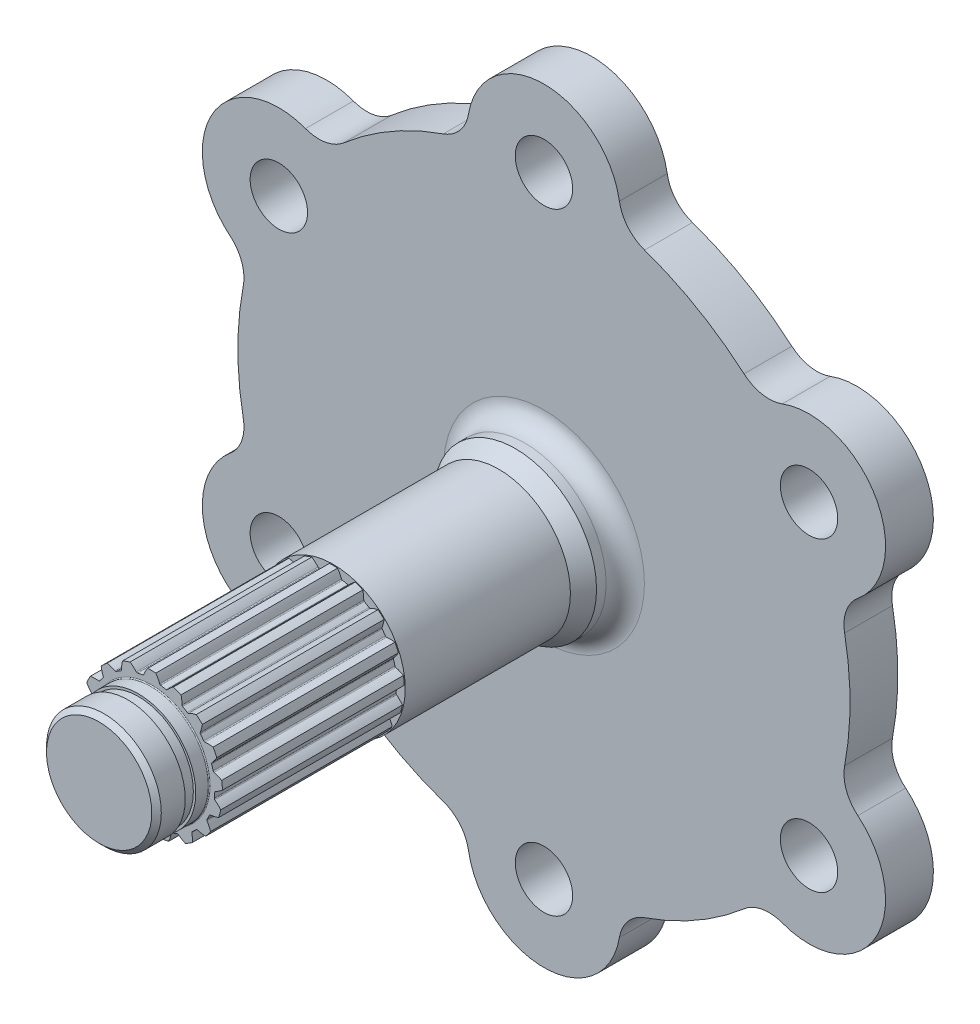
SolidWorks part; units mm, degrees
material "7075-O (SS)"
ref_plane "Front Plane" through (0, 0, 0) normal (0, 0, 1) x (1, 0, 0)
ref_plane "Top Plane" through (0, 0, 0) normal (0, 1, 0) x (1, 0, 0)
ref_plane "Right Plane" through (0, 0, 0) normal (1, 0, 0) x (0, 0, -1)
sketch "Sketch1" plane through (0, 0, 0) normal (0, 0, 1) x (1, 0, 0)
  line L0 (0, -55) -> (0, 55) construction
  line L1 (0, 40) -> (0, 0) construction
  line L2 (0, 0) -> (0, -40) construction
  circle A1 centre (0, 32) radius 3
  circle A2 centre (0, 0) radius 41.3
  circle A3 centre (27.7128, 16) radius 3
  circle A4 centre (0, 0) radius 41.3
  circle A5 centre (27.7128, -16) radius 3
  circle A6 centre (0, 0) radius 41.3
  circle A7 centre (0, -32) radius 3
  circle A8 centre (0, 0) radius 41.3
  circle A9 centre (-27.7128, -16) radius 3
  circle A10 centre (0, 0) radius 41.3
  circle A11 centre (-27.7128, 16) radius 3
  arc A12 (-7.9373, 31) -> (-22.8782, 22.3739) centre (0, 0) ccw
  arc A13 (7.9373, 31) -> (-7.9373, 31) centre (0, 32) ccw
  arc A14 (30.8154, 8.6261) -> (22.8782, 22.3739) centre (27.7128, 16) ccw
  arc A15 (22.8782, -22.3739) -> (30.8154, -8.6261) centre (27.7128, -16) ccw
  arc A16 (-7.9373, -31) -> (7.9373, -31) centre (0, -32) ccw
  arc A17 (-30.8154, -8.6261) -> (-22.8782, -22.3739) centre (-27.7128, -16) ccw
  arc A18 (-22.8782, 22.3739) -> (-30.8154, 8.6261) centre (-27.7128, 16) ccw
  circle A19 centre (0, 32) radius 8 construction
  arc A20 (-22.8782, -22.3739) -> (-7.9373, -31) centre (0, 0) ccw
  arc A21 (30.8154, -8.6261) -> (30.8154, 8.6261) centre (0, 0) ccw
  arc A22 (-30.8154, 8.6261) -> (-30.8154, -8.6261) centre (0, 0) ccw
  arc A23 (7.9373, -31) -> (22.8782, -22.3739) centre (0, 0) ccw
  arc A25 (22.8782, 22.3739) -> (7.9373, 31) centre (0, 0) ccw
  point P25 (0, 0)
  point P38 (0, 0)
  dimension "D1" = 32
  dimension "D5" = 6
  dimension "D6" = 64
  dimension "D3" = 5
  dimension "D2" = 6
  dimension "D4" = 6
extrude "Boss-Extrude1" add sketch "Sketch1" along normal blind 5 contours A11 A9 A7 A5 A3 A1 region at (0, 0, 0)
sketch "Sketch3" plane through (0, 0, 5) normal (0, 0, 1) x (1, 0, 0)
  circle A0 centre (0, 0) radius 7.5
  dimension "D1" = 15
extrude "Boss-Extrude2" add sketch "Sketch3" along normal blind 22
sketch "Sketch9" plane through (0, 0, 27) normal (0, 0, 1) x (1, 0, 0)
  arc A42 (3.0654, 6.727) -> (2.2666, 7.0365) centre (0, 0) ccw
  arc A43 (1.4878, 6.4262) -> (1.2121, 6.4839) centre (0, 0) ccw
  arc A44 (1.2121, 6.4839) -> (0.9342, 6.5297) centre (0, 0) ccw
  arc A45 (0.4284, 7.3801) -> (-0.4283, 7.3801) centre (0, 0) ccw
  arc A46 (-0.9341, 6.5297) -> (-1.212, 6.4839) centre (0, 0) ccw
  arc A47 (-1.212, 6.4839) -> (-1.4877, 6.4262) centre (0, 0) ccw
  arc A48 (-2.2665, 7.0365) -> (-3.0654, 6.727) centre (0, 0) ccw
  arc A49 (-3.2298, 5.7513) -> (-3.4724, 5.6082) centre (0, 0) ccw
  arc A50 (-3.4724, 5.6082) -> (-3.7087, 5.4549) centre (0, 0) ccw
  arc A51 (-4.6554, 5.7425) -> (-5.2885, 5.1654) centre (0, 0) ccw
  arc A52 (-5.0894, 4.1962) -> (-5.2639, 3.9751) centre (0, 0) ccw
  arc A53 (-5.2639, 3.9751) -> (-5.4288, 3.7468) centre (0, 0) ccw
  arc A54 (-6.4154, 3.6731) -> (-6.7973, 2.9062) centre (0, 0) ccw
  arc A55 (-6.2615, 2.0744) -> (-6.3444, 1.8052) centre (0, 0) ccw
  arc A56 (-6.3444, 1.8052) -> (-6.4156, 1.5327) centre (0, 0) ccw
  arc A57 (-7.3091, 1.1075) -> (-7.3881, 0.2544) centre (0, 0) ccw
  arc A58 (-6.588, -0.3276) -> (-6.568, -0.6086) centre (0, 0) ccw
  arc A59 (-6.568, -0.6086) -> (-6.5361, -0.8884) centre (0, 0) ccw
  arc A60 (-7.2156, -1.6076) -> (-6.9811, -2.4316) centre (0, 0) ccw
  arc A61 (-6.0248, -2.6854) -> (-5.9046, -2.9401) centre (0, 0) ccw
  arc A62 (-5.9046, -2.9401) -> (-5.7737, -3.1895) centre (0, 0) ccw
  arc A63 (-6.1476, -4.1056) -> (-5.6313, -4.7893) centre (0, 0) ccw
  arc A64 (-4.6479, -4.6805) -> (-4.4438, -4.8746) centre (0, 0) ccw
  arc A65 (-4.4438, -4.8746) -> (-4.2317, -5.0599) centre (0, 0) ccw
  arc A66 (-4.2493, -6.0491) -> (-3.5209, -6.5001) centre (0, 0) ccw
  arc A67 (-2.6432, -6.0434) -> (-2.3828, -6.1507) centre (0, 0) ccw
  arc A68 (-2.3828, -6.1507) -> (-2.1181, -6.2469) centre (0, 0) ccw
  arc A69 (-1.7771, -7.1757) -> (-0.935, -7.3331) centre (0, 0) ccw
  arc A70 (-0.2816, -6.5901) -> (0, -6.5962) centre (0, 0.0001) ccw
  arc A71 (0, -6.5962) -> (0.2816, -6.5901) centre (0, 0.0001) ccw
  arc A72 (0.935, -7.3331) -> (1.7772, -7.1757) centre (0, 0) ccw
  arc A73 (2.1181, -6.2469) -> (2.3828, -6.1507) centre (0, 0) ccw
  arc A74 (2.3828, -6.1507) -> (2.6432, -6.0434) centre (0, 0) ccw
  arc A75 (3.5209, -6.5001) -> (4.2493, -6.0491) centre (0, 0) ccw
  arc A76 (4.2317, -5.0599) -> (4.4438, -4.8746) centre (0, 0) ccw
  arc A77 (4.4438, -4.8746) -> (4.6479, -4.6805) centre (0, 0) ccw
  arc A78 (5.6313, -4.7893) -> (6.1476, -4.1056) centre (0, 0) ccw
  arc A79 (5.7738, -3.1895) -> (5.9047, -2.9401) centre (0, 0) ccw
  arc A80 (5.9047, -2.9401) -> (6.0248, -2.6854) centre (0, 0) ccw
  arc A81 (6.9811, -2.4316) -> (7.2156, -1.6076) centre (0, 0) ccw
  arc A82 (6.5361, -0.8884) -> (6.5681, -0.6086) centre (0, 0) ccw
  arc A83 (6.5681, -0.6086) -> (6.5881, -0.3276) centre (0, 0) ccw
  arc A84 (7.3881, 0.2544) -> (7.3091, 1.1075) centre (0, 0) ccw
  arc A85 (6.4157, 1.5327) -> (6.3444, 1.8052) centre (0, 0) ccw
  arc A86 (6.3444, 1.8052) -> (6.2615, 2.0744) centre (0, 0) ccw
  arc A87 (6.7973, 2.9062) -> (6.4155, 3.6731) centre (0, 0) ccw
  arc A88 (5.4288, 3.7468) -> (5.2639, 3.9751) centre (0, 0) ccw
  arc A89 (5.2639, 3.9751) -> (5.0894, 4.1962) centre (0, 0) ccw
  arc A90 (5.2885, 5.1654) -> (4.6554, 5.7425) centre (0, 0) ccw
  arc A91 (3.7087, 5.4549) -> (3.4725, 5.6082) centre (0, 0) ccw
  arc A92 (3.4725, 5.6082) -> (3.2299, 5.7513) centre (0, 0) ccw
  spline S0 degree 3 poles (3.2299, 5.7513) (3.2097, 5.7626) (3.1758, 5.7963) (3.1637, 5.8426) (3.1639, 5.8657) knots 0 0 0 0 0.499566 1 1 1 1
  spline S1 degree 6 poles (3.1639, 5.8657) (3.1648, 5.9848) (3.1603, 6.1142) (3.1493, 6.2536) (3.1305, 6.4026) (3.1029, 6.5607) (3.0654, 6.727) knots 0 0 0 0 0 0 0 1 1 1 1 1 1 1
  spline S2 degree 6 poles (2.2666, 7.0365) (2.1268, 6.9388) (2, 6.8406) (1.8857, 6.7431) (1.7836, 6.6475) (1.6931, 6.5549) (1.6136, 6.4663) knots 0 0 0 0 0 0 0 1 1 1 1 1 1 1
  spline S3 degree 3 poles (1.6136, 6.4663) (1.5982, 6.4491) (1.558, 6.423) (1.5102, 6.421) (1.4878, 6.4262) knots 0 0 0 0 0.500434 1 1 1 1
  spline S4 degree 3 poles (0.9342, 6.5297) (0.9113, 6.5329) (0.8675, 6.5521) (0.8395, 6.5909) (0.8313, 6.6126) knots 0 0 0 0 0.499566 1 1 1 1
  spline S5 degree 6 poles (0.8313, 6.6126) (0.7891, 6.7239) (0.7382, 6.8429) (0.6775, 6.969) (0.6062, 7.1011) (0.5234, 7.2385) (0.4284, 7.3801) knots 0 0 0 0 0 0 0 1 1 1 1 1 1 1
  spline S6 degree 6 poles (-0.4283, 7.3801) (-0.5234, 7.2385) (-0.6062, 7.1011) (-0.6775, 6.969) (-0.7382, 6.8429) (-0.7891, 6.7239) (-0.8313, 6.6126) knots 0 0 0 0 0 0 0 1 1 1 1 1 1 1
  spline S7 degree 3 poles (-0.8313, 6.6126) (-0.8394, 6.5909) (-0.8674, 6.5521) (-0.9113, 6.5329) (-0.9341, 6.5297) knots 0 0 0 0 0.500434 1 1 1 1
  spline S8 degree 3 poles (-1.4877, 6.4262) (-1.5102, 6.421) (-1.558, 6.423) (-1.5981, 6.4491) (-1.6135, 6.4663) knots 0 0 0 0 0.499566 1 1 1 1
  spline S9 degree 6 poles (-1.6135, 6.4663) (-1.6931, 6.5549) (-1.7836, 6.6475) (-1.8857, 6.7431) (-1.9999, 6.8406) (-2.1268, 6.9388) (-2.2665, 7.0365) knots 0 0 0 0 0 0 0 1 1 1 1 1 1 1
  spline S10 degree 6 poles (-3.0654, 6.727) (-3.1029, 6.5607) (-3.1305, 6.4026) (-3.1492, 6.2536) (-3.1603, 6.1142) (-3.1648, 5.9848) (-3.1639, 5.8657) knots 0 0 0 0 0 0 0 1 1 1 1 1 1 1
  spline S11 degree 3 poles (-3.1639, 5.8657) (-3.1637, 5.8426) (-3.1757, 5.7963) (-3.2097, 5.7626) (-3.2298, 5.7513) knots 0 0 0 0 0.500434 1 1 1 1
  spline S12 degree 3 poles (-3.7087, 5.4549) (-3.7277, 5.4418) (-3.7731, 5.4265) (-3.8199, 5.4363) (-3.8405, 5.4468) knots 0 0 0 0 0.499566 1 1 1 1
  spline S13 degree 6 poles (-3.8405, 5.4468) (-3.9467, 5.5007) (-4.0645, 5.5543) (-4.1942, 5.6066) (-4.336, 5.6562) (-4.4897, 5.7019) (-4.6554, 5.7425) knots 0 0 0 0 0 0 0 1 1 1 1 1 1 1
  spline S14 degree 6 poles (-5.2885, 5.1654) (-5.2633, 4.9967) (-5.232, 4.8394) (-5.1956, 4.6937) (-5.1556, 4.5597) (-5.113, 4.4374) (-5.0692, 4.3267) knots 0 0 0 0 0 0 0 1 1 1 1 1 1 1
  spline S15 degree 3 poles (-5.0692, 4.3267) (-5.0606, 4.3052) (-5.0552, 4.2577) (-5.0746, 4.214) (-5.0894, 4.1962) knots 0 0 0 0 0.500434 1 1 1 1
  spline S16 degree 3 poles (-5.4288, 3.7468) (-5.4418, 3.7278) (-5.4785, 3.6971) (-5.5257, 3.6893) (-5.5487, 3.6917) knots 0 0 0 0 0.499566 1 1 1 1
  spline S17 degree 6 poles (-5.5487, 3.6917) (-5.6672, 3.7035) (-5.7965, 3.711) (-5.9363, 3.7128) (-6.0864, 3.7079) (-6.2463, 3.695) (-6.4154, 3.6731) knots 0 0 0 0 0 0 0 1 1 1 1 1 1 1
  spline S18 degree 6 poles (-6.7973, 2.9062) (-6.7129, 2.758) (-6.6268, 2.6226) (-6.5403, 2.4998) (-6.4546, 2.3894) (-6.3707, 2.2907) (-6.2898, 2.2033) knots 0 0 0 0 0 0 0 1 1 1 1 1 1 1
  spline S19 degree 3 poles (-6.2898, 2.2033) (-6.2741, 2.1864) (-6.2518, 2.144) (-6.2542, 2.0962) (-6.2615, 2.0744) knots 0 0 0 0 0.500434 1 1 1 1
  spline S20 degree 3 poles (-6.4156, 1.5327) (-6.421, 1.5102) (-6.4441, 1.4683) (-6.4853, 1.444) (-6.5076, 1.4379) knots 0 0 0 0 0.499566 1 1 1 1
  spline S21 degree 6 poles (-6.5076, 1.4379) (-6.6224, 1.4062) (-6.7456, 1.3665) (-6.8767, 1.3177) (-7.0149, 1.2588) (-7.1593, 1.1891) (-7.3091, 1.1075) knots 0 0 0 0 0 0 0 1 1 1 1 1 1 1
  spline S22 degree 6 poles (-7.3881, 0.2544) (-7.2559, 0.1468) (-7.1267, 0.0516) (-7.0017, -0.0316) (-6.8818, -0.1036) (-6.768, -0.1653) (-6.661, -0.2176) knots 0 0 0 0 0 0 0 1 1 1 1 1 1 1
  spline S23 degree 3 poles (-6.661, -0.2176) (-6.6402, -0.2277) (-6.6042, -0.2592) (-6.5891, -0.3046) (-6.588, -0.3276) knots 0 0 0 0 0.500434 1 1 1 1
  spline S24 degree 3 poles (-6.5361, -0.8884) (-6.5329, -0.9113) (-6.5394, -0.9587) (-6.569, -0.9963) (-6.5876, -1.01) knots 0 0 0 0 0.499566 1 1 1 1
  spline S25 degree 6 poles (-6.5876, -1.01) (-6.6831, -1.081) (-6.7837, -1.1626) (-6.8883, -1.2555) (-6.9959, -1.3602) (-7.1054, -1.4775) (-7.2156, -1.6076) knots 0 0 0 0 0 0 0 1 1 1 1 1 1 1
  spline S26 degree 6 poles (-6.9811, -2.4316) (-6.8189, -2.4843) (-6.6641, -2.5263) (-6.5175, -2.5588) (-6.3797, -2.5826) (-6.2512, -2.5991) (-6.1326, -2.6092) knots 0 0 0 0 0 0 0 1 1 1 1 1 1 1
  spline S27 degree 3 poles (-6.1326, -2.6092) (-6.1096, -2.6111) (-6.0646, -2.6274) (-6.0341, -2.6643) (-6.0248, -2.6854) knots 0 0 0 0 0.500434 1 1 1 1
  spline S28 degree 3 poles (-5.7737, -3.1895) (-5.7625, -3.2097) (-5.7514, -3.2563) (-5.7655, -3.302) (-5.7779, -3.3215) knots 0 0 0 0 0.499566 1 1 1 1
  spline S29 degree 6 poles (-5.7779, -3.3215) (-5.8413, -3.4223) (-5.9056, -3.5347) (-5.9696, -3.659) (-6.0321, -3.7956) (-6.0918, -3.9445) (-6.1476, -4.1056) knots 0 0 0 0 0 0 0 1 1 1 1 1 1 1
  spline S30 degree 6 poles (-5.6313, -4.7893) (-5.461, -4.7798) (-5.3015, -4.7631) (-5.153, -4.7404) (-5.0159, -4.7128) (-4.8902, -4.6818) (-4.7759, -4.6483) knots 0 0 0 0 0 0 0 1 1 1 1 1 1 1
  spline S31 degree 3 poles (-4.7759, -4.6483) (-4.7538, -4.6418) (-4.7059, -4.6407) (-4.6642, -4.6642) (-4.6479, -4.6805) knots 0 0 0 0 0.500434 1 1 1 1
  spline S32 degree 3 poles (-4.2317, -5.0599) (-4.2139, -5.0746) (-4.1867, -5.114) (-4.1834, -5.1618) (-4.1878, -5.1844) knots 0 0 0 0 0.499566 1 1 1 1
  spline S33 degree 6 poles (-4.1878, -5.1844) (-4.2106, -5.3013) (-4.2299, -5.4293) (-4.2447, -5.5684) (-4.2536, -5.7183) (-4.2556, -5.8787) (-4.2493, -6.0491) knots 0 0 0 0 0 0 0 1 1 1 1 1 1 1
  spline S34 degree 6 poles (-3.5209, -6.5001) (-3.3656, -6.4298) (-3.2228, -6.3566) (-3.0926, -6.2818) (-2.9747, -6.2066) (-2.8687, -6.1322) (-2.7742, -6.0597) knots 0 0 0 0 0 0 0 1 1 1 1 1 1 1
  spline S35 degree 3 poles (-2.7742, -6.0597) (-2.7559, -6.0456) (-2.7117, -6.0273) (-2.6643, -6.0341) (-2.6432, -6.0434) knots 0 0 0 0 0.500434 1 1 1 1
  spline S36 degree 3 poles (-2.1181, -6.2469) (-2.0962, -6.2542) (-2.0566, -6.2811) (-2.0362, -6.3244) (-2.0322, -6.3472) knots 0 0 0 0 0.499566 1 1 1 1
  spline S37 degree 6 poles (-2.0322, -6.3472) (-2.0112, -6.4644) (-1.983, -6.5907) (-1.9465, -6.7258) (-1.9007, -6.8688) (-1.8445, -7.0191) (-1.7771, -7.1757) knots 0 0 0 0 0 0 0 1 1 1 1 1 1 1
  spline S38 degree 6 poles (-0.935, -7.3331) (-0.8156, -7.2114) (-0.7089, -7.0916) (-0.6145, -6.9747) (-0.5317, -6.862) (-0.4598, -6.7544) (-0.3979, -6.6527) knots 0 0 0 0 0 0 0 1 1 1 1 1 1 1
  spline S39 degree 3 poles (-0.3979, -6.6527) (-0.3859, -6.6329) (-0.3513, -6.5999) (-0.3046, -6.5891) (-0.2816, -6.5901) knots 0 0 0 0 0.500434 1 1 1 1
  spline S40 degree 3 poles (0.2816, -6.5901) (0.3047, -6.5891) (0.3513, -6.5999) (0.3859, -6.6329) (0.3979, -6.6527) knots 0 0 0 0 0.499566 1 1 1 1
  spline S41 degree 6 poles (0.3979, -6.6527) (0.4598, -6.7544) (0.5318, -6.862) (0.6146, -6.9747) (0.709, -7.0916) (0.8156, -7.2114) (0.935, -7.3331) knots 0 0 0 0 0 0 0 1 1 1 1 1 1 1
  spline S42 degree 6 poles (1.7772, -7.1757) (1.8446, -7.0191) (1.9007, -6.8688) (1.9465, -6.7258) (1.983, -6.5907) (2.0112, -6.4644) (2.0322, -6.3472) knots 0 0 0 0 0 0 0 1 1 1 1 1 1 1
  spline S43 degree 3 poles (2.0322, -6.3472) (2.0362, -6.3244) (2.0566, -6.2811) (2.0962, -6.2542) (2.1181, -6.2469) knots 0 0 0 0 0.500434 1 1 1 1
  spline S44 degree 3 poles (2.6432, -6.0434) (2.6644, -6.0341) (2.7117, -6.0273) (2.756, -6.0456) (2.7743, -6.0597) knots 0 0 0 0 0.499566 1 1 1 1
  spline S45 degree 6 poles (2.7743, -6.0597) (2.8687, -6.1322) (2.9747, -6.2066) (3.0926, -6.2818) (3.2229, -6.3566) (3.3656, -6.4298) (3.5209, -6.5001) knots 0 0 0 0 0 0 0 1 1 1 1 1 1 1
  spline S46 degree 6 poles (4.2493, -6.0491) (4.2556, -5.8787) (4.2537, -5.7183) (4.2447, -5.5684) (4.23, -5.4293) (4.2106, -5.3013) (4.1879, -5.1844) knots 0 0 0 0 0 0 0 1 1 1 1 1 1 1
  spline S47 degree 3 poles (4.1879, -5.1844) (4.1834, -5.1618) (4.1868, -5.114) (4.214, -5.0746) (4.2317, -5.0599) knots 0 0 0 0 0.500434 1 1 1 1
  spline S48 degree 3 poles (4.6479, -4.6805) (4.6642, -4.6642) (4.706, -4.6407) (4.7538, -4.6418) (4.7759, -4.6483) knots 0 0 0 0 0.499566 1 1 1 1
  spline S49 degree 6 poles (4.7759, -4.6483) (4.8902, -4.6818) (5.0159, -4.7128) (5.153, -4.7404) (5.3015, -4.7631) (5.461, -4.7798) (5.6313, -4.7893) knots 0 0 0 0 0 0 0 1 1 1 1 1 1 1
  spline S50 degree 6 poles (6.1476, -4.1056) (6.0919, -3.9445) (6.0321, -3.7956) (5.9696, -3.659) (5.9056, -3.5347) (5.8413, -3.4223) (5.7779, -3.3215) knots 0 0 0 0 0 0 0 1 1 1 1 1 1 1
  spline S51 degree 3 poles (5.7779, -3.3215) (5.7655, -3.302) (5.7515, -3.2563) (5.7626, -3.2097) (5.7738, -3.1895) knots 0 0 0 0 0.500434 1 1 1 1
  spline S52 degree 3 poles (6.0248, -2.6854) (6.0342, -2.6643) (6.0646, -2.6274) (6.1096, -2.6111) (6.1326, -2.6092) knots 0 0 0 0 0.499566 1 1 1 1
  spline S53 degree 6 poles (6.1326, -2.6092) (6.2513, -2.5991) (6.3797, -2.5826) (6.5175, -2.5588) (6.6641, -2.5263) (6.819, -2.4843) (6.9811, -2.4316) knots 0 0 0 0 0 0 0 1 1 1 1 1 1 1
  spline S54 degree 6 poles (7.2156, -1.6076) (7.1054, -1.4775) (6.9959, -1.3602) (6.8883, -1.2555) (6.7837, -1.1626) (6.6832, -1.081) (6.5876, -1.01) knots 0 0 0 0 0 0 0 1 1 1 1 1 1 1
  spline S55 degree 3 poles (6.5876, -1.01) (6.569, -0.9963) (6.5394, -0.9587) (6.5329, -0.9113) (6.5361, -0.8884) knots 0 0 0 0 0.500434 1 1 1 1
  spline S56 degree 3 poles (6.5881, -0.3276) (6.5892, -0.3046) (6.6042, -0.2592) (6.6403, -0.2277) (6.661, -0.2176) knots 0 0 0 0 0.499566 1 1 1 1
  spline S57 degree 6 poles (6.661, -0.2176) (6.768, -0.1653) (6.8819, -0.1036) (7.0017, -0.0316) (7.1268, 0.0516) (7.2559, 0.1468) (7.3881, 0.2544) knots 0 0 0 0 0 0 0 1 1 1 1 1 1 1
  spline S58 degree 6 poles (7.3091, 1.1075) (7.1593, 1.1891) (7.0149, 1.2588) (6.8767, 1.3177) (6.7456, 1.3665) (6.6224, 1.4062) (6.5076, 1.4379) knots 0 0 0 0 0 0 0 1 1 1 1 1 1 1
  spline S59 degree 3 poles (6.5076, 1.4379) (6.4853, 1.444) (6.4441, 1.4683) (6.421, 1.5102) (6.4157, 1.5327) knots 0 0 0 0 0.500434 1 1 1 1
  spline S60 degree 3 poles (6.2615, 2.0744) (6.2542, 2.0962) (6.2519, 2.144) (6.2741, 2.1864) (6.2899, 2.2033) knots 0 0 0 0 0.499566 1 1 1 1
  spline S61 degree 6 poles (6.2899, 2.2033) (6.3707, 2.2907) (6.4546, 2.3894) (6.5403, 2.4998) (6.6269, 2.6226) (6.7129, 2.758) (6.7973, 2.9062) knots 0 0 0 0 0 0 0 1 1 1 1 1 1 1
  spline S62 degree 6 poles (6.4155, 3.6731) (6.2464, 3.695) (6.0865, 3.7079) (5.9363, 3.7128) (5.7965, 3.711) (5.6672, 3.7035) (5.5488, 3.6917) knots 0 0 0 0 0 0 0 1 1 1 1 1 1 1
  spline S63 degree 3 poles (5.5488, 3.6917) (5.5258, 3.6893) (5.4786, 3.6971) (5.4418, 3.7278) (5.4288, 3.7468) knots 0 0 0 0 0.500434 1 1 1 1
  spline S64 degree 3 poles (5.0894, 4.1962) (5.0747, 4.214) (5.0552, 4.2577) (5.0606, 4.3052) (5.0692, 4.3267) knots 0 0 0 0 0.499566 1 1 1 1
  spline S65 degree 6 poles (5.0692, 4.3267) (5.113, 4.4374) (5.1556, 4.5597) (5.1957, 4.6937) (5.232, 4.8394) (5.2633, 4.9967) (5.2885, 5.1654) knots 0 0 0 0 0 0 0 1 1 1 1 1 1 1
  spline S66 degree 6 poles (4.6554, 5.7425) (4.4898, 5.7019) (4.336, 5.6562) (4.1943, 5.6066) (4.0645, 5.5543) (3.9467, 5.5007) (3.8405, 5.4468) knots 0 0 0 0 0 0 0 1 1 1 1 1 1 1
  spline S67 degree 3 poles (3.8405, 5.4468) (3.8199, 5.4363) (3.7731, 5.4265) (3.7278, 5.4418) (3.7087, 5.4549) knots 0 0 0 0 0.500434 1 1 1 1
extrude "Boss-Extrude7" add sketch "Sketch9" along normal blind 19
sketch "Sketch4" plane through (0, 0, 46) normal (0, 0, 1) x (1, 0, 0)
  circle A0 centre (0, 0) radius 6
  dimension "D2" = 12
extrude "Boss-Extrude3" add sketch "Sketch4" along normal blind 5.5
sketch "Sketch6" plane through (0, 0, 5) normal (0, 0, 1) x (1, 0, 0)
  circle A0 centre (0, 0) radius 8.5
  dimension "D1" = 17
extrude "Boss-Extrude5" add sketch "Sketch6" along normal blind 3
fillet "Fillet1" radius 2 1 edges at (8.5, 0, 5)
chamfer "Chamfer2" distance 1 angle 60 1 edges at (7.5, 0, 8) first distance on face at (7.5, 0, 8)
chamfer "Chamfer3" distance 0.5 angle 45 1 edges at (6, 0, 51.5)
fillet "Fillet2" radius 0.1 1 edges at (6, 0, 46)
fillet "Fillet3" radius 4 12 edges at (22.8782, -22.3739, 2.5) (7.9373, -31, 2.5) (-7.9373, -31, 2.5) (-22.8782, -22.3739, 2.5) (-30.8154, -8.6261, 2.5) (-30.8154, 8.6261, 2.5) (-22.8782, 22.3739, 2.5) (-7.9373, 31, 2.5) (7.9373, 31, 2.5) (30.8154, -8.6261, 2.5) (30.8154, 8.6261, 2.5) (22.8782, 22.3739, 2.5)
sketch "Sketch12" plane through (0, 0, 0) normal (1, 0, 0) x (0, 0, -1)
  line L0 (-47.4, 6) -> (-47.4, 5.75)
  line L1 (-47.4, 5.75) -> (-48.5, 5.75)
  line L2 (-48.5, 5.75) -> (-48.5, 6)
  line L4 (-46.1, 6) -> (-46.1, -6) construction
  line L5 (-51.5, 0) -> (-46.1, 0) construction
  line L6 (-51.5, 5.5) -> (-51.5, -5.5) construction
  line L7 (-47.4, 6) -> (-48.5, 6)
  dimension "D1" = 1.3
  dimension "D2" = 1.1
  dimension "D3" = 5.75
  dimension "D4" = 0.25
  dimension "D5" = 6
revolve "Cut-Revolve1" cut sketch "Sketch12" angle 360 about L5
sketch "Sketch13" plane through (0, 0, 0) normal (0, 0, -1) x (-1, 0, 0)
  circle A0 centre (0, 0) radius 24
  circle A1 centre (0, 0) radius 21
  dimension "D2" = 48
  dimension "D1" = 3
extrude "Boss-Extrude8" add sketch "Sketch13" along normal blind 4
chamfer "Chamfer4" distance 1 angle 45 2 edges at (-24, 0, -4) (-21, 0, 0)
fillet "Fillet4" [suppressed] radius 0.2
